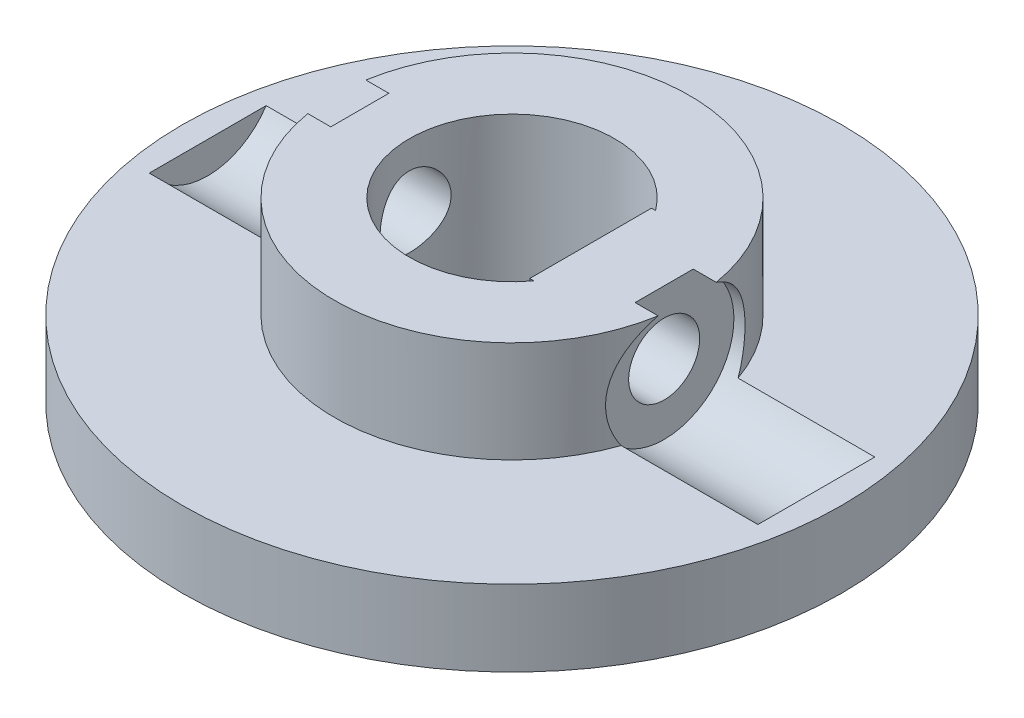
SolidWorks part; units mm, degrees
ref_plane "Front Plane" through (0, 0, 0) normal (0, 0, 1) x (1, 0, 0)
ref_plane "Top Plane" through (0, 0, 0) normal (0, 1, 0) x (1, 0, 0)
ref_plane "Right Plane" through (0, 0, 0) normal (1, 0, 0) x (0, 0, -1)
sketch "Stock_horn_drive_flange_profile" plane through (0, 0, 0) normal (0, 1, 0) x (1, 0, 0)
  circle A0 centre (0, 0) radius 13
  circle A1 centre (0, 0) radius 4.05
  dimension "D1" = 26
  dimension "D2" = 8.1
extrude "Stock_horn_drive_flange" add sketch "Stock_horn_drive_flange_profile" along normal blind 3 from offset 41
sketch "D_coupling_ring_profile" plane through (0, 0, 0) normal (0, 1, 0) x (1, 0, 0)
  circle A0 centre (0, 0) radius 7
  circle A1 centre (0, 0) radius 4.05
  dimension "D1" = 14
  dimension "D2" = 8.1
extrude "D_coupling_ring" add sketch "D_coupling_ring_profile" along normal blind 4 from offset 44
sketch "D_key_land_profile" plane through (0, 0, 0) normal (0, 1, 0) x (1, 0, 0)
  line L1 (3.1, -2.4) -> (6, -2.4)
  line L2 (3.1, -2.4) -> (3.1, 2.4)
  line L3 (3.1, 2.4) -> (6, 2.4)
  line L4 (6, -2.4) -> (6, 2.4)
  dimension "D1" = 2.9
  dimension "D2" = 4.8
  dimension "D3" = 3.1
  dimension "D4" = 2.4
extrude "D_key_land" add sketch "D_key_land_profile" along normal blind 4 from offset 44
sketch "Captured_horn_key_boss_profile" plane through (0, 0, 0) normal (0, 1, 0) x (1, 0, 0)
  circle A0 centre (0, 0) radius 13
  dimension "D1" = 26
extrude "Captured_horn_key_boss_SUPERSEDED_owned_servo" [suppressed] add sketch "Captured_horn_key_boss_profile" along normal blind 1.65 from offset 39.35
sketch "Stock_horn_pocket_Hub" plane through (0, 0, 0) normal (0, 1, 0) x (1, 0, 0)
  circle A0 centre (0, 0) radius 3.55
  dimension "D1" = 7.1
extrude "Key_pocket_Hub_SUPERSEDED_owned_servo" [suppressed] cut sketch "Stock_horn_pocket_Hub" along normal blind 1.65 from offset 39.35
sketch "Stock_horn_pocket_Horizontal" plane through (0, 0, 0) normal (0, 1, 0) x (1, 0, 0)
  line L1 (-8.15, -2.1) -> (8.15, -2.1)
  line L2 (-8.15, -2.1) -> (-8.15, 2.1)
  line L3 (-8.15, 2.1) -> (8.15, 2.1)
  line L4 (8.15, -2.1) -> (8.15, 2.1)
  dimension "D1" = 16.3
  dimension "D2" = 4.2
  dimension "D3" = 8.15
  dimension "D4" = 2.1
extrude "Key_pocket_Horizontal_SUPERSEDED_owned_servo" [suppressed] cut sketch "Stock_horn_pocket_Horizontal" along normal blind 1.65 from offset 39.35
sketch "Stock_horn_pocket_Vertical" plane through (0, 0, 0) normal (0, 1, 0) x (1, 0, 0)
  line L1 (-2.1, -8.15) -> (2.1, -8.15)
  line L2 (-2.1, -8.15) -> (-2.1, 8.15)
  line L3 (-2.1, 8.15) -> (2.1, 8.15)
  line L4 (2.1, -8.15) -> (2.1, 8.15)
  dimension "D1" = 4.2
  dimension "D2" = 16.3
  dimension "D3" = 2.1
  dimension "D4" = 8.15
extrude "Key_pocket_Vertical_SUPERSEDED_owned_servo" [suppressed] cut sketch "Stock_horn_pocket_Vertical" along normal blind 1.65 from offset 39.35
sketch "Stock_horn_pocket_Rounded_tips" plane through (0, 0, 0) normal (0, 1, 0) x (1, 0, 0)
  circle A0 centre (8.15, 0) radius 2.1
  circle A1 centre (-8.15, 0) radius 2.1
  circle A2 centre (0, 8.15) radius 2.1
  circle A3 centre (0, -8.15) radius 2.1
  dimension "D1" = 4.2
  dimension "D2" = 4.2
  dimension "D3" = 4.2
  dimension "D4" = 4.2
  dimension "D5" = 8.15
  dimension "D6" = 8.15
  dimension "D7" = 8.15
  dimension "D8" = 8.15
extrude "Key_pocket_Rounded_tips_SUPERSEDED_owned_servo" [suppressed] cut sketch "Stock_horn_pocket_Rounded_tips" along normal blind 1.65 from offset 39.35
sketch "Unmodified_horn_capture_M2_profile" plane through (0, 0, 0) normal (0, 1, 0) x (1, 0, 0)
  circle A0 centre (7, 7) radius 1.15
  circle A1 centre (-7, 7) radius 1.15
  circle A2 centre (-7, -7) radius 1.15
  circle A3 centre (7, -7) radius 1.15
  dimension "D1" = 2.3
  dimension "D2" = 2.3
  dimension "D3" = 2.3
  dimension "D4" = 2.3
  dimension "D5" = 7
  dimension "D6" = 7
  dimension "D7" = 7
  dimension "D8" = 7
extrude "Unmodified_horn_capture_M2_SUPERSEDED_owned_servo" [suppressed] cut sketch "Unmodified_horn_capture_M2_profile" along normal through all from offset 50 offset against normal yes
sketch "Horn_center_hub_clearance" plane through (0, 0, 0) normal (0, 1, 0) x (1, 0, 0)
  circle A0 centre (0, 0) radius 4
  dimension "D1" = 8
extrude "Hub_clearance_in_key_boss_only_SUPERSEDED_owned_servo" [suppressed] cut sketch "Horn_center_hub_clearance" along normal blind 1.65 from offset 39.35
sketch "Yaw_positive_retention_crossbolt_profile" plane through (0, 0, 0) normal (1, 0, 0) x (0, 0, -1)
  circle A0 centre (0, 45.5) radius 1.1
  dimension "D1" = 2.2
  dimension "D2" = 45.5
extrude "Yaw_positive_retention_crossbolt" cut sketch "Yaw_positive_retention_crossbolt_profile" along normal through all from offset 10 offset against normal yes
sketch "Crossbolt_flat_seat_-12" plane through (0, 0, 0) normal (1, 0, 0) x (0, 0, -1)
  circle A0 centre (0, 45.5) radius 2.75
  dimension "D1" = 5.5
  dimension "D2" = 45.5
extrude "Crossbolt_flat_seat_cut_-12" cut sketch "Crossbolt_flat_seat_-12" along normal blind 6 from offset 12 offset against normal yes
sketch "Crossbolt_flat_seat_6" plane through (0, 0, 0) normal (1, 0, 0) x (0, 0, -1)
  circle A0 centre (0, 45.5) radius 2.75
  dimension "D1" = 5.5
  dimension "D2" = 45.5
extrude "Crossbolt_flat_seat_cut_6" cut sketch "Crossbolt_flat_seat_6" along normal blind 6 from offset 6
sketch "SG90_spline_socket_boss_profile" plane through (0, 0, 0) normal (0, 1, 0) x (1, 0, 0)
  circle A0 centre (0, 0) radius 6
  dimension "D1" = 12
extrude "SG90_spline_socket_boss_OD12" add sketch "SG90_spline_socket_boss_profile" along normal blind 3.7 from offset 37.3
sketch "SG90_spline_press_socket_D4p85_depth2p5_profile" plane through (0, 0, 0) normal (0, 1, 0) x (1, 0, 0)
  circle A0 centre (0, 0) radius 2.425
  dimension "D1" = 4.85
extrude "SG90_spline_press_socket_D4p85_depth2p5" cut sketch "SG90_spline_press_socket_D4p85_depth2p5_profile" along normal blind 2.5 from offset 37.3
sketch "SG90_centre_screw_clearance_D2p4_profile" plane through (0, 0, 0) normal (0, 1, 0) x (1, 0, 0)
  circle A0 centre (0, 0) radius 1.2
  dimension "D1" = 2.4
extrude "SG90_centre_screw_clearance_D2p4" cut sketch "SG90_centre_screw_clearance_D2p4_profile" along normal blind 1.2 from offset 39.8
sketch "Crossbolt_axial_float_clearance_D2p8_profile" plane through (0, 0, 0) normal (1, 0, 0) x (0, 0, -1)
  circle A0 centre (0, 45.5) radius 1.4
  dimension "D1" = 2.8
  dimension "D2" = 45.5
extrude "Crossbolt_axial_float_clearance_D2p8" cut sketch "Crossbolt_axial_float_clearance_D2p8_profile" along normal through all from offset 10 offset against normal yes
